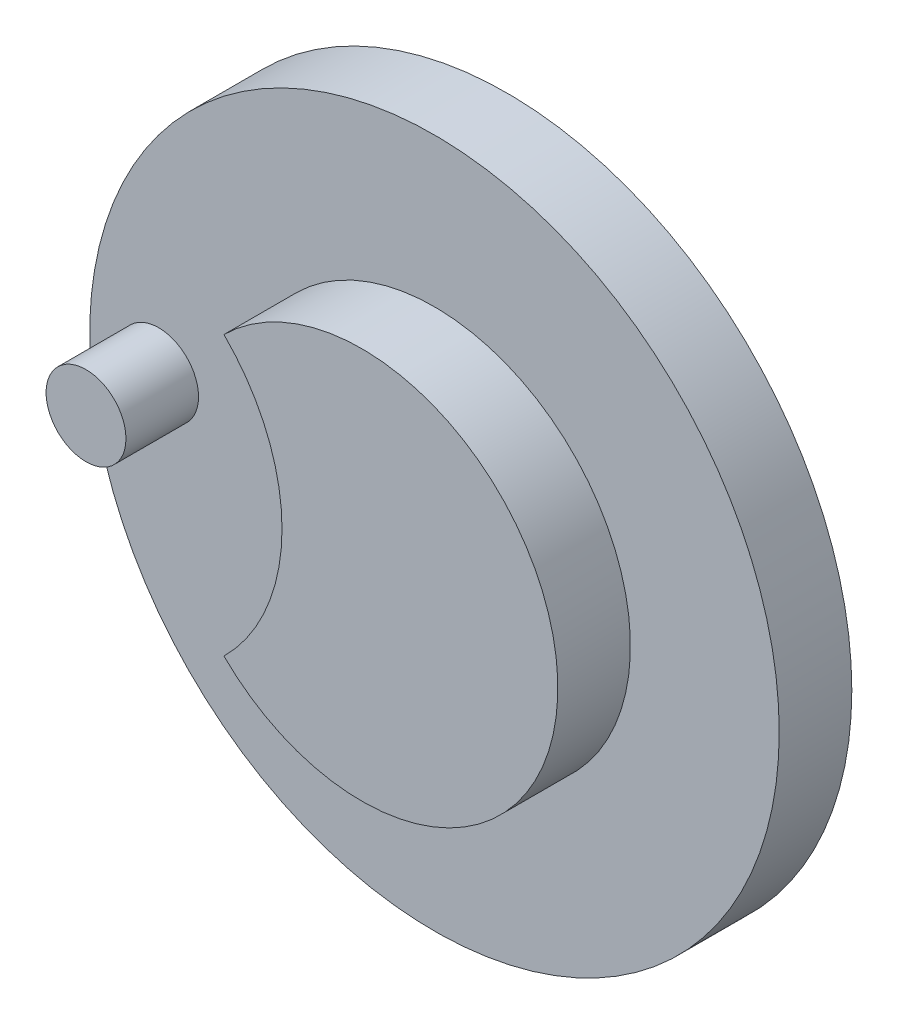
SolidWorks part; units mm, degrees
ref_plane "Alzado" through (0, 0, 0) normal (0, 0, 1) x (1, 0, 0)
ref_plane "Planta" through (0, 0, 0) normal (0, 1, 0) x (1, 0, 0)
ref_plane "Vista lateral" through (0, 0, 0) normal (1, 0, 0) x (0, 0, -1)
sketch "Croquis2" plane through (0, 0, 0) normal (0, 0, 1) x (1, 0, 0)
  circle A0 centre (0, 0) radius 38 construction
  arc A1 (-19, -19.1833) -> (-19, 19.1833) centre (0, 0) ccw
  circle A3 centre (0, 0) radius 47.5
  arc A5 (-19, -19.1833) -> (-19, 19.1833) centre (-38, 0) ccw
  circle A6 centre (-38, 0) radius 5.5
  dimension "D1" = 27
  dimension "D2" = 76
  dimension "D3" = 95
  dimension "D4" = 27
  dimension "D5" = 11
extrude "Saliente-Extruir1" add sketch "Croquis2" along normal blind 10 contours A3 A6 A1 A5 region at (-46.1565, 0, 0)
extrude "Saliente-Extruir2" add sketch "Croquis2<4>" along normal blind 20 contours A6 | A5 A1 region at (4.3061, 0, 0) region at (-38, 0, 0)
sketch "Croquis2<4>" plane through (0, 0, 0) normal (0, 0, 1) x (1, 0, 0) same geometry as "Croquis2"
sketch "Croquis6" plane through (0, 0, 0) normal (0, 0, -1) x (-1, 0, 0)
  circle A0 centre (0, 0) radius 5
  dimension "D1" = 10
extrude "Saliente-Extruir3" add sketch "Croquis6" along normal blind 10
